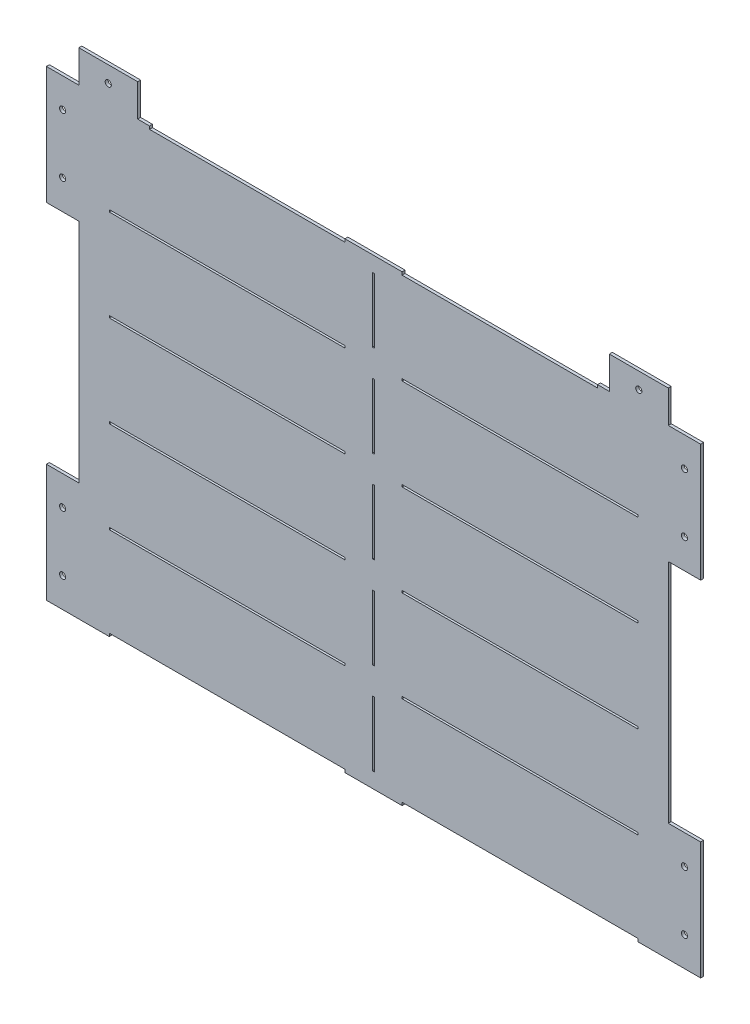
SolidWorks part; units mm, degrees
material "6061-T6 (SS)"
ref_plane "X-Y Datum" through (0, 0, 0) normal (0, 0, 1) x (1, 0, 0)
ref_plane "X-Z Datum" through (0, 0, 0) normal (0, 1, 0) x (1, 0, 0)
ref_plane "Y-Z Datum" through (0, 0, 0) normal (1, 0, 0) x (0, 0, -1)
sketch "Master Sketch" plane through (0, 0, 0) normal (0, 0, 1) x (1, 0, 0)
  line L0 (1.143, 50.5714) -> (314.5028, 50.5714) construction
  line L1 (-317.6778, 249.174) -> (317.6778, 249.174)
  line L2 (-317.6778, 249.174) -> (-317.6778, -249.174)
  line L3 (-317.6778, -249.174) -> (317.6778, -249.174)
  line L4 (317.6778, 249.174) -> (317.6778, -249.174)
  line L5 (-317.6778, 249.174) -> (317.6778, -249.174) construction
  line L6 (-317.6778, -249.174) -> (317.6778, 249.174) construction
  line L7 (-1.143, 249.174) -> (1.143, 249.174) construction
  line L8 (-1.143, 249.174) -> (-1.143, -249.174) construction
  line L9 (-1.143, -249.174) -> (1.143, -249.174) construction
  line L10 (1.143, 249.174) -> (1.143, -249.174) construction
  line L11 (-1.143, 249.174) -> (1.143, -249.174) construction
  line L12 (-1.143, -249.174) -> (1.143, 249.174) construction
  line L13 (1.143, 245.999) -> (314.5028, 245.999) construction
  line L14 (1.143, 245.999) -> (1.143, 149.4282) construction
  line L15 (1.143, 149.4282) -> (314.5028, 149.4282) construction
  line L16 (314.5028, 245.999) -> (314.5028, 149.4282) construction
  line L17 (1.143, 245.999) -> (314.5028, 149.4282) construction
  line L18 (1.143, 149.4282) -> (314.5028, 245.999) construction
  line L19 (1.143, 147.1422) -> (314.5028, 147.1422) construction
  line L20 (314.5028, 147.1422) -> (314.5028, 50.5714) construction
  line L21 (1.143, 147.1422) -> (1.143, 50.5714) construction
  line L22 (1.143, -48.2854) -> (314.5028, -48.2854) construction
  line L23 (1.143, 48.2854) -> (314.5028, 48.2854) construction
  line L24 (314.5028, 48.2854) -> (314.5028, -48.2854) construction
  line L25 (1.143, 48.2854) -> (1.143, -48.2854) construction
  line L26 (1.143, -147.1422) -> (314.5028, -147.1422) construction
  line L27 (1.143, -50.5714) -> (314.5028, -50.5714) construction
  line L28 (314.5028, -50.5714) -> (314.5028, -147.1422) construction
  line L29 (1.143, -50.5714) -> (1.143, -147.1422) construction
  line L30 (1.143, -245.999) -> (314.5028, -245.999) construction
  line L31 (1.143, -149.4282) -> (314.5028, -149.4282) construction
  line L32 (314.5028, -149.4282) -> (314.5028, -245.999) construction
  line L33 (1.143, -149.4282) -> (1.143, -245.999) construction
  line L34 (0, 249.174) -> (0, -249.174) construction
  line L35 (-1.143, -149.4282) -> (-1.143, -245.999) construction
  line L36 (-314.5028, -149.4282) -> (-314.5028, -245.999) construction
  line L37 (-1.143, -149.4282) -> (-314.5028, -149.4282) construction
  line L38 (-1.143, -245.999) -> (-314.5028, -245.999) construction
  line L39 (-1.143, -50.5714) -> (-1.143, -147.1422) construction
  line L40 (-314.5028, -50.5714) -> (-314.5028, -147.1422) construction
  line L41 (-1.143, -50.5714) -> (-314.5028, -50.5714) construction
  line L42 (-1.143, -147.1422) -> (-314.5028, -147.1422) construction
  line L43 (-1.143, 48.2854) -> (-1.143, -48.2854) construction
  line L44 (-314.5028, 48.2854) -> (-314.5028, -48.2854) construction
  line L45 (-1.143, 48.2854) -> (-314.5028, 48.2854) construction
  line L46 (-1.143, -48.2854) -> (-314.5028, -48.2854) construction
  line L47 (-1.143, 147.1422) -> (-1.143, 50.5714) construction
  line L48 (-314.5028, 147.1422) -> (-314.5028, 50.5714) construction
  line L49 (-1.143, 147.1422) -> (-314.5028, 147.1422) construction
  line L50 (-1.143, 149.4282) -> (-314.5028, 245.999) construction
  line L51 (-1.143, 245.999) -> (-314.5028, 149.4282) construction
  line L52 (-314.5028, 245.999) -> (-314.5028, 149.4282) construction
  line L53 (-1.143, 149.4282) -> (-314.5028, 149.4282) construction
  line L54 (-1.143, 245.999) -> (-1.143, 149.4282) construction
  line L55 (-1.143, 245.999) -> (-314.5028, 245.999) construction
  line L56 (-1.143, 249.174) -> (-1.143, -249.174) construction
  line L57 (-1.143, 50.5714) -> (-314.5028, 50.5714) construction
  line L59 (2.413, -152.8699) -> (313.2328, -152.8699) construction
  line L60 (2.413, -152.8699) -> (2.413, -242.5573) construction
  line L61 (2.413, -242.5573) -> (313.2328, -242.5573) construction
  line L62 (313.2328, -152.8699) -> (313.2328, -242.5573) construction
  line L63 (2.413, -152.8699) -> (313.2328, -242.5573) construction
  line L64 (2.413, -242.5573) -> (313.2328, -152.8699) construction
  point P0 (0, 0)
  point P6 (0, 0)
  point P11 (157.8229, 197.7136)
  point P54 (-157.8229, 197.7136)
  point P55 (157.8229, -197.7136)
  point P60 (157.8229, -149.4282)
  point P61 (314.5028, -197.7136)
  point P62 (-314.5028, 98.8568)
  point P63 (-314.5028, 0)
  dimension "D1" = 3.175
  dimension "D2" = 498.348
  dimension "D3" = 2.286
  dimension "D4" = 313.3598
  dimension "D5" = 96.5708
  dimension "D6" = 3.175
  dimension "D7" = 5
  dimension "D8" = 2.286
  dimension "D9" = 89.6874
  dimension "D10" = 310.8198
  dimension "D11" = 98.8568
  dimension "D12" = 635.3556
extrude "Boss-Extrude1" add sketch "Master Sketch" along normal blind 3.175
sketch "Sketch2" plane through (0, 0, 3.175) normal (0, 0, 1) x (1, 0, 0)
  line L0 (0, 317.2302) -> (0, -317.2302) construction
  line L1 (-352.6028, -185.674) -> (-317.6778, -185.674) construction
  line L6 (-335.1403, -122.174) -> (-335.1403, -185.674) construction
  line L7 (-380.7135, 0) -> (380.7135, 0) construction
  line L8 (-335.1403, -185.674) -> (-335.1403, -153.924) construction
  line L9 (-335.1403, -122.174) -> (-335.1403, -249.174) construction
  line L10 (-317.6778, -249.174) -> (-352.6028, -249.174)
  line L11 (-317.6778, -249.174) -> (-317.6778, -122.174)
  line L12 (-317.6778, -122.174) -> (-352.6028, -122.174)
  line L13 (-352.6028, -249.174) -> (-352.6028, -122.174)
  line L14 (-335.1403, -153.924) -> (-315.5316, -153.924) construction
  circle A6 centre (-335.1403, -153.924) radius 3 construction
  circle A8 centre (-335.1403, -217.424) radius 3 construction
  point P4 (0, 0)
  point P18 (0, 0)
  dimension "D8" = 34.925
  dimension "D1" = 6
  dimension "D9" = 127
extrude "Boss-Extrude2" add sketch "Sketch2" against normal blind 3.175
hole_wizard "M6 Clearance Hole1" positions "Sketch3" profile "Sketch4" hole size "M6" standard "ANSI Metric" end condition through all
sketch "Sketch3" plane through (0, 0, 3.175) normal (0, 0, 1) x (1, 0, 0)
  point P47 (-335.1403, -217.424)
  point P50 (-335.1403, -153.924)
sketch "Sketch4" plane through (-335.1403, -217.424, 3.175) normal (1, 0, 0) x (0, -1, 0)
  line L0 (0, 0) -> (0, 3.175)
  line L1 (0, 3.175) -> (3.3, 3.175)
  line L2 (3.3, 3.175) -> (3.3, 0)
  line L5 (3.3, 0) -> (0, 0)
  line L11 (0, -6.35) -> (0, 107.95) construction
  dimension "Thru Hole Dia." = 6.6
  dimension "Thru Hole Depth" = 3.175
mirror "Mirror1" about plane through (0, 0, 0) normal (1, 0, 0) of "Boss-Extrude2", "M6 Clearance Hole1"
mirror "Mirror7" about plane through (0, 0, 0) normal (0, 1, 0) of "Mirror1", "Boss-Extrude2", "M6 Clearance Hole1"
sketch "Sketch5" plane through (0, 0, 3.175) normal (0, 0, 1) x (1, 0, 0)
  line L5 (-1.143, 232.6386) -> (1.143, 232.6386)
  line L6 (-1.143, 232.6386) -> (-1.143, 162.7886)
  line L7 (-1.143, 162.7886) -> (1.143, 162.7886)
  line L8 (1.143, 232.6386) -> (1.143, 162.7886)
  line L9 (-157.8229, 197.7136) -> (157.8229, 197.7136) construction
  line L10 (-1.143, 232.6386) -> (1.143, 162.7886) construction
  line L11 (-1.143, 162.7886) -> (1.143, 232.6386) construction
  point P0 (0, 0)
  point P1 (0, 197.7136)
  dimension "D1" = 2.286
  dimension "D2" = 69.85
extrude "Cut-Extrude1" cut sketch "Sketch5" against normal through all
pattern_linear "LPattern1" count 5 spacing 98.8568 along (0, -1, 0) of "Cut-Extrude1"
sketch "Sketch7" plane through (0, 0, 3.175) normal (0, 0, 1) x (1, 0, 0)
  line L0 (-157.8229, 149.4282) -> (-157.8229, 147.1422) construction
  line L1 (-1.143, 149.4282) -> (-314.5028, 149.4282) construction
  line L2 (-1.143, 147.1422) -> (-314.5028, 147.1422) construction
  line L3 (-157.8229, 50.5714) -> (-157.8229, 48.2854) construction
  line L4 (-284.8229, 149.4282) -> (-30.8229, 149.4282)
  line L5 (-284.8229, 149.4282) -> (-284.8229, 147.1422)
  line L6 (-284.8229, 147.1422) -> (-30.8229, 147.1422)
  line L7 (-30.8229, 149.4282) -> (-30.8229, 147.1422)
  line L8 (-284.8229, 149.4282) -> (-30.8229, 147.1422) construction
  line L9 (-284.8229, 147.1422) -> (-30.8229, 149.4282) construction
  line L10 (-1.143, 50.5714) -> (-314.5028, 50.5714) construction
  line L11 (-1.143, 48.2854) -> (-314.5028, 48.2854) construction
  point P6 (-157.8229, 148.2852)
  dimension "D1" = 2.286
  dimension "D2" = 254
extrude "Cut-Extrude3" cut sketch "Sketch7" against normal through all
pattern_linear "LPattern2" count 4 spacing 98.8568 along (0, -1, 0) of "Cut-Extrude3"
mirror "Mirror4" about plane through (0, 0, 0) normal (1, 0, 0) of "LPattern2", "Cut-Extrude3"
sketch "Sketch10" plane through (0, 0, 3.175) normal (0, 0, 1) x (1, 0, 0)
  line L0 (-317.6778, 122.174) -> (-317.6778, 249.174) construction
  line L5 (352.6028, 249.174) -> (-352.6028, 249.174) construction
  line L6 (-317.6778, 266.6365) -> (-254.1778, 266.6365) construction
  line L9 (-317.6778, 249.174) -> (-254.1778, 249.174)
  line L10 (-317.6778, 249.174) -> (-317.6778, 284.099)
  line L11 (-317.6778, 284.099) -> (-254.1778, 284.099)
  line L12 (-254.1778, 249.174) -> (-254.1778, 284.099)
  circle A4 centre (-285.9278, 266.6365) radius 3
  dimension "D1" = 6
  dimension "D4" = 34.925
  dimension "D5" = 63.5
extrude "Boss-Extrude3" add sketch "Sketch10" against normal blind 3.175
hole_wizard "M6 Clearance Hole2" positions "Sketch11" profile "Sketch12" hole size "M6" standard "ANSI Metric" end condition through all
sketch "Sketch11" plane through (0, 0, 3.175) normal (0, 0, 1) x (1, 0, 0)
  point P16 (-285.9278, 266.6365)
sketch "Sketch12" plane through (-285.9278, 266.6365, 3.175) normal (1, 0, 0) x (0, -1, 0)
  line L0 (0, 0) -> (0, 3.175)
  line L1 (0, 3.175) -> (3.3, 3.175)
  line L2 (3.3, 3.175) -> (3.3, 0)
  line L5 (3.3, 0) -> (0, 0)
  line L11 (0, -6.35) -> (0, 107.95) construction
  dimension "Thru Hole Dia." = 6.6
  dimension "Thru Hole Depth" = 3.175
mirror "Mirror6" about plane through (0, 0, 0) normal (1, 0, 0) of "M6 Clearance Hole2", "Boss-Extrude3"
sketch "Sketch6" plane through (0, 0, 3.175) normal (0, 0, 1) x (1, 0, 0)
  line L0 (-157.8229, 245.999) -> (-157.8229, 249.174) construction
  line L1 (-1.143, 245.999) -> (-314.5028, 245.999) construction
  line L2 (-317.6778, 249.174) -> (317.6778, 249.174) construction
  line L3 (0, -78.309) -> (0, 78.309) construction
  line L4 (-284.8229, 249.174) -> (-30.8229, 249.174)
  line L5 (-284.8229, 249.174) -> (-284.8229, 245.999)
  line L6 (-284.8229, 245.999) -> (-30.8229, 245.999)
  line L7 (-30.8229, 249.174) -> (-30.8229, 245.999)
  line L8 (-284.8229, 249.174) -> (-30.8229, 245.999) construction
  line L9 (-284.8229, 245.999) -> (-30.8229, 249.174) construction
  line L10 (30.8229, 249.174) -> (30.8229, 245.999)
  line L11 (284.8229, 249.174) -> (30.8229, 249.174)
  line L12 (284.8229, 245.999) -> (30.8229, 245.999)
  line L13 (284.8229, 249.174) -> (284.8229, 245.999)
  line L14 (1.7463, 0) -> (-1.7463, 0) construction
  line L15 (-284.8229, -245.999) -> (-30.8229, -249.174) construction
  line L16 (-284.8229, -249.174) -> (-30.8229, -245.999) construction
  line L17 (-157.8229, -245.999) -> (-157.8229, -249.174) construction
  line L18 (284.8229, -249.174) -> (284.8229, -245.999)
  line L19 (284.8229, -245.999) -> (30.8229, -245.999)
  line L20 (284.8229, -249.174) -> (30.8229, -249.174)
  line L21 (30.8229, -249.174) -> (30.8229, -245.999)
  line L22 (-30.8229, -249.174) -> (-30.8229, -245.999)
  line L23 (-284.8229, -245.999) -> (-30.8229, -245.999)
  line L24 (-284.8229, -249.174) -> (-284.8229, -245.999)
  line L25 (-284.8229, -249.174) -> (-30.8229, -249.174)
  line L26 (-241.4778, 245.999) -> (-241.4778, 249.174)
  line L27 (-254.1778, 249.174) -> (-254.1778, 284.099) construction
  line L28 (241.4778, 245.999) -> (241.4778, 249.174)
  point P6 (-157.8229, 247.5865)
  point P29 (-157.8229, -247.5865)
  dimension "D1" = 3.175
  dimension "D2" = 254
  dimension "D3" = 12.7
extrude "Cut-Extrude2" cut sketch "Sketch6" against normal through all contours L24 L22 L23 | L21 L18 L19 | L26 L6 L7 L4 | L12 L28 L11 L10 region at (-136.1504, 247.5865, 3.175) region at (136.1504, 247.5865, 3.175) region at (157.8229, -247.5865, 3.175) region at (-157.8229, -247.5865, 3.175)
sketch "Sketch13" plane through (0, 0, 0) normal (0, 0, -1) x (-1, 0, 0)
  line L0 (352.6028, -122.174) -> (352.6028, -249.174) construction
  line L1 (254.1778, 284.099) -> (317.6778, 284.099) construction
  circle A0 centre (335.1403, -153.924) radius 3.3 construction
  circle A1 centre (285.9278, 266.6365) radius 3.3 construction
  point P0 (338.4403, -153.924)
  point P5 (285.9278, 269.9365)
  dimension "D1" = 14.1625
  dimension "D2" = 14.1625
